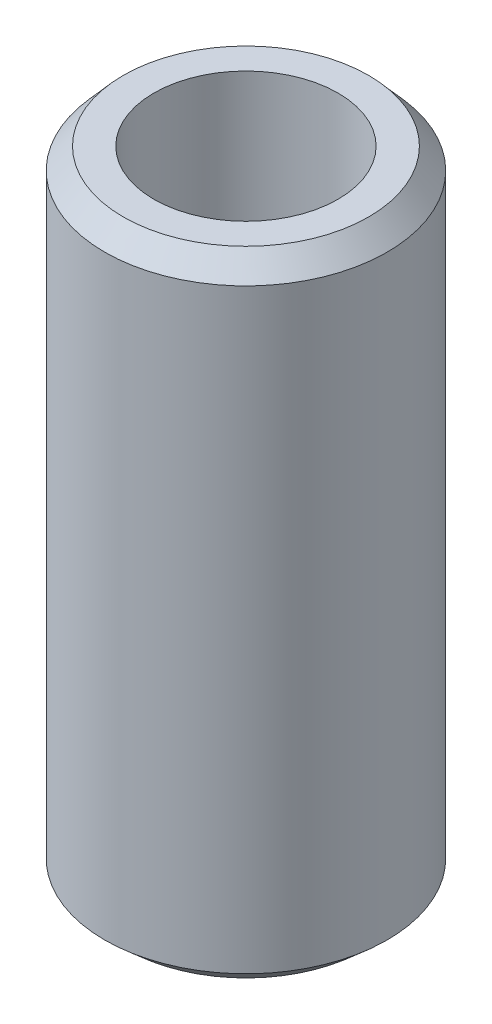
SolidWorks part; units mm, degrees
ref_plane "Front Plane" through (0, 0, 0) normal (0, 0, 1) x (1, 0, 0)
ref_plane "Top Plane" through (0, 0, 0) normal (0, 1, 0) x (1, 0, 0)
ref_plane "Right Plane" through (0, 0, 0) normal (1, 0, 0) x (0, 0, -1)
sketch "Sketch1" plane through (0, 0, 0) normal (0, 1, 0) x (1, 0, 0)
  circle A0 centre (0, 0) radius 40
  dimension "SHAFT_OD" = 80
extrude "Boss-Extrude1" add sketch "Sketch1" along normal blind 179.9364
sketch "Sketch2" plane through (0, 0, 0) normal (0, 1, 0) x (1, 0, 0)
  circle A0 centre (0, 0) radius 26.0682
  dimension "BORE_D" = 52.1363
extrude "Cut-Extrude1" cut sketch "Sketch2" along normal through all
chamfer "Chamfer1" distance 5.9918 angle 41.314 2 edges at (0, 179.9364, 40) (0, 0, 40) first distance on face at (0, 179.9364, 40) first distance on face at (0, 0, 26.0682)
